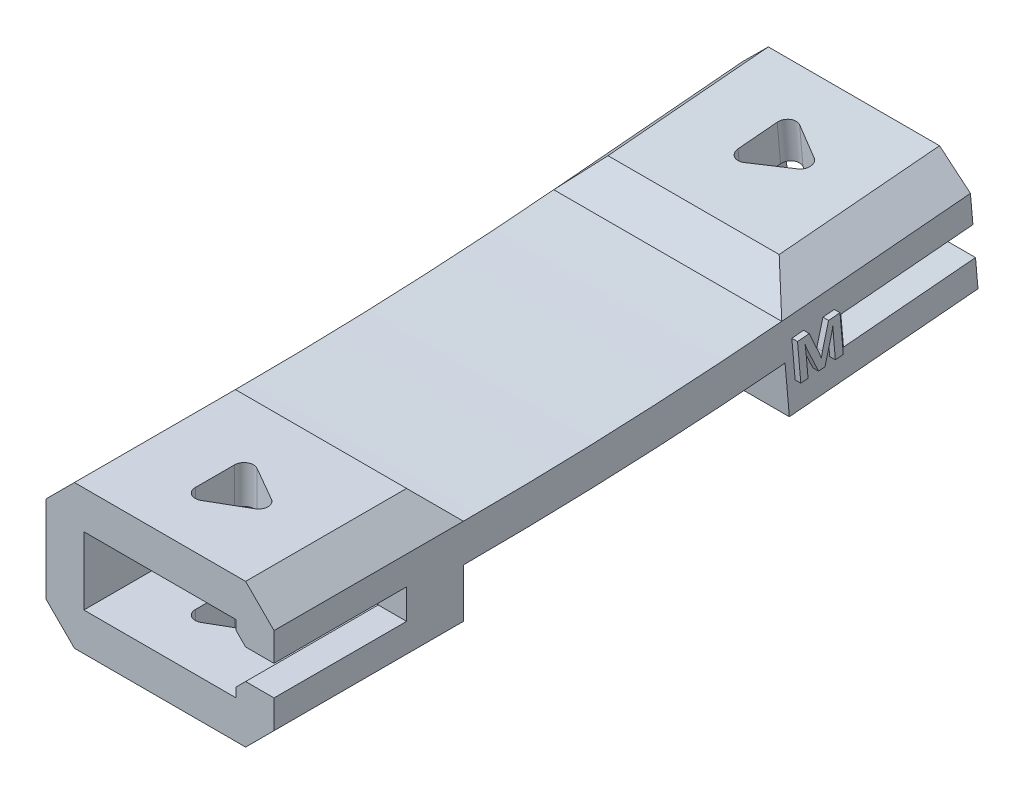
SolidWorks part; units mm, degrees
note: The reader was unsure of these and kept them because the rebuilt part matched: shared geometry of "Sketch1<2>", "Sketch5<4>".
ref_plane "Front Plane" through (0, 0, 0) normal (0, 0, 1) x (1, 0, 0)
ref_plane "Top Plane" through (0, 0, 0) normal (0, 1, 0) x (1, 0, 0)
ref_plane "Right Plane" through (0, 0, 0) normal (1, 0, 0) x (0, 0, -1)
other "Configuration Table"
sketch "Sketch1" plane through (0, 0, 0) normal (0, 0, 1) x (1, 0, 0)
  line L1 (4.02, -1.79) -> (-4.02, -1.79)
  line L2 (4.02, -1.79) -> (4.02, 1.79)
  line L3 (4.02, 1.79) -> (-4.02, 1.79)
  line L4 (-4.02, -1.79) -> (-4.02, 1.79)
  line L5 (0, 1.79) -> (0, -1.79) construction
  line L6 (4.02, 0) -> (-4.02, 0) construction
  line L7 (-6.02, 3.79) -> (6.02, 3.79)
  line L8 (-6.02, 3.79) -> (-6.02, -3.79)
  line L9 (-6.02, -3.79) -> (6.02, -3.79)
  line L10 (6.02, 3.79) -> (6.02, -3.79)
  line L11 (0, -3.79) -> (0, 3.79) construction
  line L12 (-6.02, 0) -> (6.02, 0) construction
  point P0 (0, 0)
  point P4 (0, 0)
  dimension "D1" = 3.58
  dimension "D2" = 8.04
  dimension "D3" = 2
  dimension "D4" = 2
extrude "Boss-Extrude1" add sketch "Sketch1" along normal blind 8
extrude "Boss-Extrude2" add sketch "Sketch1<2>" against normal blind 2 contours L4 L1 L2 L3 | L10 L7 L8 L9 L1 L4 L3 L2
sketch "Sketch1<2>" plane through (0, 0, 0) normal (0, 0, 1) x (1, 0, 0) same geometry as "Sketch1"
sketch "Sketch3" plane through (6.02, 9.81, 0) normal (1, 0, 0) x (0, -1, 0)
  line L0 (13.6, 2) -> (9.52, 2)
  line L2 (8.7785, 18.9838) -> (12.8429, 19.3394)
  line L3 (13.6, -8) -> (13.6, 2) construction
  arc A1 (9.52, 2) -> (8.7785, 18.9838) centre (-185.3477, 2) ccw
  arc A3 (12.8429, 19.3394) -> (13.6, 2) centre (-185.3477, 2) cw construction
  dimension "D1" = 4.08
  dimension "D4" = 5
  dimension "D2" = 17
extrude "Extrude-Thin1" add sketch "Sketch3" along normal up to surface (12.04 mm away) thin contours L0 A1 L2
sketch "Sketch5" plane through (0, -2.0948, -19.2573) normal (0, 0.0872, -0.9962) x (-1, 0, 0)
  line L1 (4.02, 1.0583) -> (-4.02, 1.0583)
  line L2 (4.02, 1.0583) -> (4.02, 4.6383)
  line L3 (4.02, 4.6383) -> (-4.02, 4.6383)
  line L4 (-4.02, 1.0583) -> (-4.02, 4.6383)
  line L5 (0, 4.6383) -> (0, 1.0583) construction
  line L6 (4.02, 2.8483) -> (-4.02, 2.8483) construction
  line L7 (-6.02, 6.6383) -> (6.02, 6.6383)
  line L8 (-6.02, 6.6383) -> (-6.02, -0.9417)
  line L9 (-6.02, -0.9417) -> (6.02, -0.9417)
  line L10 (6.02, 6.6383) -> (6.02, -0.9417)
  line L11 (0, -0.9417) -> (0, 6.6383) construction
  line L12 (-6.02, 2.8483) -> (6.02, 2.8483) construction
  line L13 (6.02, -0.9417) -> (-6.02, -0.9417) construction
  point P0 (0, 2.8483)
  point P4 (0, 2.8483)
  dimension "D1" = 3.58
  dimension "D2" = 8.04
  dimension "D3" = 2
  dimension "D4" = 2
extrude "Boss-Extrude4" add sketch "Sketch5" along normal blind 10
extrude "Boss-Extrude5" add sketch "Sketch5<4>" along normal blind 2 contours L8 L7 L10 L9
sketch "Sketch5<4>" plane through (0, -2.0948, -19.2573) normal (0, 0.0872, -0.9962) x (-1, 0, 0) same geometry as "Sketch5"
chamfer "Chamfer1" distance 1.5 angle 45 12 edges at (6.02, -2.5972, -24.3204) (6.02, 4.954, -23.6597) (-6.02, 4.954, -23.6597) (-6.02, -2.5972, -24.3204) (6.02, 3.79, 3) (6.02, -3.79, 3) (-6.02, -3.79, 3) (-6.02, 3.79, 3) (0, 3.79, -2) (0, -3.0329, -19.3394) (0, -3.79, -2) (0, 4.5182, -18.6788)
sketch "Sketch6" plane through (0, 3.79, 0) normal (0, 1, 0) x (1, 0, 0)
  line L0 (0, 2) -> (0, -8) construction
  line L4 (1.45, -3.567) -> (-0.35, -2.5278)
  line L5 (-1.1, -2.9608) -> (-1.1, -5.0392)
  line L6 (-0.35, -5.4722) -> (1.45, -4.433)
  line L7 (-6.02, 2) -> (6.02, 2) construction
  line L8 (4.52, -8) -> (-4.52, -8) construction
  line L9 (4.02, 0) -> (-4.02, 0) construction
  circle A0 centre (0, -4) radius 1.1 construction
  arc A1 (-1.1, -5.0392) -> (-0.35, -5.4722) centre (-0.6, -5.0392) ccw
  arc A2 (-0.35, -2.5278) -> (-1.1, -2.9608) centre (-0.6, -2.9608) ccw
  arc A3 (1.45, -3.567) -> (1.45, -4.433) centre (1.2, -4) cw
  point P15 (-1.1, -5.9053)
  point P18 (-1.1, -2.0947)
  dimension "D3" = 0.5
  dimension "D1" = 2.2
  dimension "D2" = 4
sketch "Sketch7" plane through (0, 2.8621, 0.2504) normal (0, 0.9962, 0.0872) x (1, 0, 0)
  line L0 (0, 29.0015) -> (0, 19.0015) construction
  line L4 (1.45, 25.4345) -> (-0.35, 26.4737)
  line L5 (-1.1, 26.0407) -> (-1.1, 23.9623)
  line L6 (-0.35, 23.5292) -> (1.45, 24.5685)
  line L7 (6.02, 19.0015) -> (-6.02, 19.0015) construction
  line L8 (4.52, 29.0015) -> (-4.52, 29.0015) construction
  line L9 (-4.02, 21.0015) -> (4.02, 21.0015) construction
  circle A0 centre (0, 25.0015) radius 1.1 construction
  arc A1 (-1.1, 23.9623) -> (-0.35, 23.5292) centre (-0.6, 23.9623) ccw
  arc A2 (1.45, 25.4345) -> (1.45, 24.5685) centre (1.2, 25.0015) cw
  arc A3 (-0.35, 26.4737) -> (-1.1, 26.0407) centre (-0.6, 26.0407) ccw
  dimension "D1" = 2.2
  dimension "D3" = 0.5
  dimension "D2" = 4
extrude "Cut-Extrude1" cut sketch "Sketch6" against normal through all both and the other way through all
extrude "Cut-Extrude2" cut sketch "Sketch7" against normal through all both and the other way through all
sketch "Sketch8" plane through (0, 2.5276, -28.8911) normal (0, 0.0872, -0.9962) x (-1, 0, 0)
  line L1 (-8.02, -0.1269) -> (-4.02, -0.1269)
  line L2 (-8.02, -0.1269) -> (-8.02, -1.7069)
  line L3 (-8.02, -1.7069) -> (-4.02, -1.7069)
  line L4 (-4.02, -0.1269) -> (-4.02, -1.7069)
  line L5 (-6.02, -1.7069) -> (-6.02, -0.1269) construction
  line L6 (-8.02, -0.9169) -> (-4.02, -0.9169) construction
  line L8 (-6.02, -3.2069) -> (-6.02, 1.3731) construction
  line L9 (-4.02, -2.7069) -> (-4.02, 0.8731) construction
  line L10 (4.02, -2.7069) -> (-4.02, -2.7069) construction
  point P0 (-6.02, -0.9169)
  dimension "D1" = 1.58
  dimension "D2" = 4
  dimension "D3" = 1
extrude "Cut-Extrude3" cut sketch "Sketch8" against normal offset from surface (7 mm away) 1 up to face at (0, 0.9169, -21.0015)
sketch "Sketch9" plane through (0, 0, 8) normal (0, 0, 1) x (1, 0, 0)
  line L1 (8.02, 0.79) -> (4.02, 0.79)
  line L2 (8.02, 0.79) -> (8.02, -0.79)
  line L3 (8.02, -0.79) -> (4.02, -0.79)
  line L4 (4.02, 0.79) -> (4.02, -0.79)
  line L5 (6.02, -0.79) -> (6.02, 0.79) construction
  line L6 (8.02, 0) -> (4.02, 0) construction
  line L8 (6.02, -2.29) -> (6.02, 2.29) construction
  line L9 (4.02, -1.79) -> (4.02, 1.79) construction
  line L10 (-4.02, -1.79) -> (4.02, -1.79) construction
  point P0 (6.02, 0)
  dimension "D1" = 1.58
  dimension "D2" = 4
  dimension "D3" = 1
extrude "Cut-Extrude4" cut sketch "Sketch9" against normal offset from surface (7 mm away) 1 up to face at (0, 0, 0)
chamfer "Chamfer2" distance 0.5 angle 45 6 edges at (4.02, 2.0961, -25.4155) (4.02, 1.0041, -21.9977) (4.02, 0.5222, -25.5532) (4.02, 0.79, 4.5) (4.02, 0, 1) (4.02, -0.79, 4.5)
sketch "Sketch10" plane through (6.02, 0, 0) normal (1, 0, 0) x (0, 0, -1)
  line L0 (22.0665, 0.2171) -> (19.0779, -0.0444) construction
  line L2 (18.9838, 1.0315) -> (19.2087, -1.5387) construction
  line L3 (22.0665, 0.2171) -> (21.9288, 1.7911) construction
  line L4 (29.0399, 0.8272) -> (22.0665, 0.2171) construction
  text T0 "<b>M</b>" font "@Microsoft YaHei" height 2
extrude "Boss-Extrude6" add sketch "Sketch10" along normal blind 0.3
sketch "Sketch11" [suppressed] plane through (6.02, 0, 0) normal (1, 0, 0) x (0, 0, -1)
  line L0 (21.0675, 0.1735) -> (18.0789, -0.088) construction
  line L1 (17.9848, 0.9879) -> (18.2096, -1.5823) construction
  line L2 (28.0408, 0.7836) -> (21.0675, 0.1735) construction
  text T0 "<b>IR</b>" font "@Microsoft YaHei" height 2
extrude "Boss-Extrude7" [suppressed] add sketch "Sketch11" along normal blind 0.3
sketch "Sketch12" [suppressed] plane through (6.02, 0, 0) normal (1, 0, 0) x (0, 0, -1)
  line L0 (19.0694, 0.0862) -> (16.0808, -0.1752) construction
  line L1 (15.9867, 0.9007) -> (16.2115, -1.6695) construction
  line L2 (26.0428, 0.6963) -> (19.0694, 0.0862) construction
  text T0 "<b>P</b>\r\n" font "@Microsoft YaHei" height 2
extrude "Boss-Extrude8" [suppressed] add sketch "Sketch12" along normal blind 0.3
equation "\"LF\" = 0.04mm"
equation "\"TF\" = 0.02mm"
equation "\"AngLF\"= 0.5"
equation "\"AngTF\"= 0.3"
equation "\"D2@Sketch1\"=8+2*\"TF\""
equation "\"D1@Sketch1\"=3.5+2*\"LF\""
